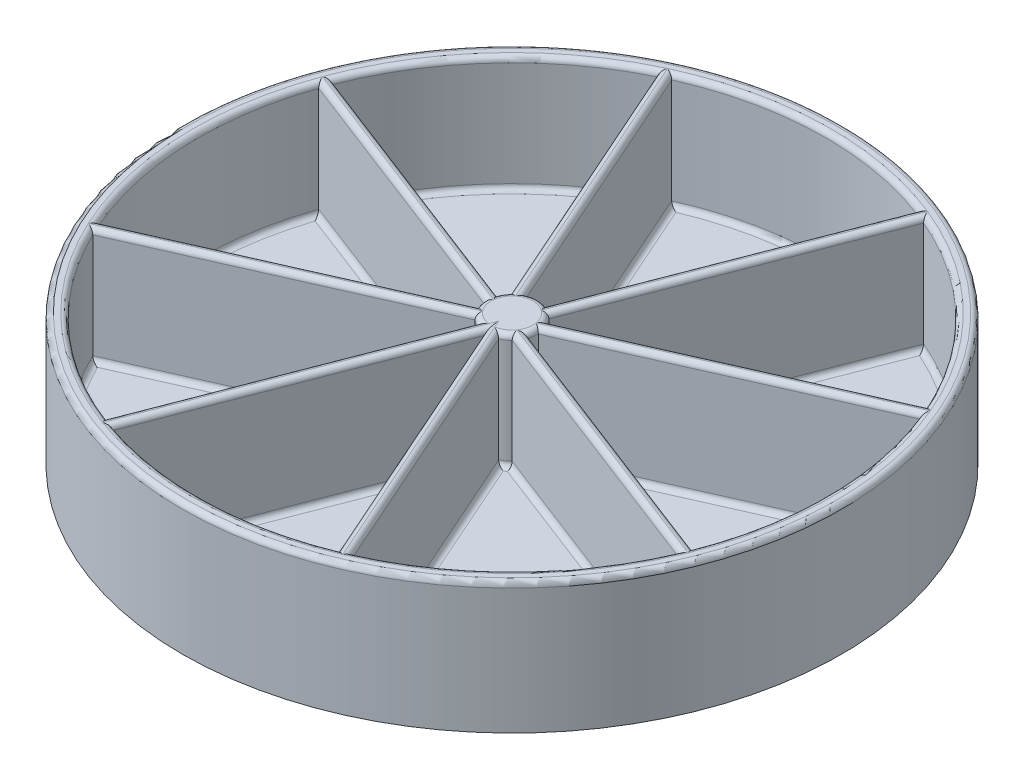
SolidWorks part; units mm, degrees
ref_plane "Front Plane" through (0, 0, 0) normal (0, 0, 1) x (1, 0, 0)
ref_plane "Top Plane" through (0, 0, 0) normal (0, 1, 0) x (1, 0, 0)
ref_plane "Right Plane" through (0, 0, 0) normal (1, 0, 0) x (0, 0, -1)
sketch "Sketch1" plane through (0, 0, 0) normal (0, 1, 0) x (1, 0, 0)
  circle A0 centre (0, 0) radius 63
extrude "Boss-Extrude1" add sketch "Sketch1" along normal blind 25
sketch "Sketch2" plane through (0, 25, 0) normal (0, 1, 0) x (1, 0, 0)
  circle A0 centre (0, 0) radius 60
extrude "Cut-Extrude1" cut sketch "Sketch2" against normal blind 22
sketch "Sketch3" plane through (0, 3, 0) normal (0, 1, 0) x (1, 0, 0)
  line L0 (-24.3169, 54.8515) -> (24.3169, -54.8515)
  line L1 (21.5912, 55.9805) -> (-24.3169, 54.8515)
  line L2 (-24.3169, 54.8515) -> (-55.9805, 21.5912)
  line L3 (-55.9805, 21.5912) -> (-54.8515, -24.3169)
  line L4 (-54.8515, -24.3169) -> (-21.5912, -55.9805)
  line L5 (-21.5912, -55.9805) -> (24.3169, -54.8515)
  line L6 (24.3169, -54.8515) -> (55.9805, -21.5912)
  line L7 (55.9805, -21.5912) -> (54.8515, 24.3169)
  line L8 (54.8515, 24.3169) -> (21.5912, 55.9805)
  line L9 (-21.5912, -55.9805) -> (21.5912, 55.9805)
  line L10 (-54.8515, -24.3169) -> (54.8515, 24.3169)
  line L11 (-55.9805, 21.5912) -> (55.9805, -21.5912)
  circle A0 centre (0, 0) radius 55.4328 construction
extrude "Extrude-Thin2" add sketch "Sketch3" along normal blind 22 thin contours L0 | L11 | L10 | L9 thin type one direction wall 2
sketch "Sketch4" plane through (0, 0, 0) normal (0, -1, 0) x (1, 0, 0)
  circle A0 centre (0, 0) radius 5
extrude "Boss-Extrude2" add sketch "Sketch4" against normal blind 25
fillet "Fillet1" radius 1 63 edges at (-11.6953, 3, 30.3228) (11.6953, 3, -30.3228) (-40.6404, 3, 44.1402) (-28.6946, 3, 14.9087) (30.3158, 3, -11.2519) (-2.6349, 3, 4.2494) (-9.7924, 3, 30.9469) (11.3017, 3, 30.4281) (1.4751, 3, 59.9819) (-30.8322, 3, -9.7481) (29.3928, 3, 13.4802) (42.761, 3, 42.0892) (-13.1716, 3, -29.7112) (13.1716, 3, 29.7112) (2.8406, 3, 4.1147) (59.9981, 3, -0.4751) (-30.3228, 3, -11.6953) (30.3228, 3, 11.6953) (4.9182, 3, 0.9009) (13.4802, 3, -29.3928) (42.0892, 3, -42.761) (-29.7112, 3, 13.1716) (29.7112, 3, -13.1716) (4.1147, 3, -2.8406) (-1.4751, 3, -59.9819) (-0.1229, 3, -4.9985) (-44.1402, 3, -40.6404) (-14.9087, 3, -28.6946) (-4.2494, 3, -2.6349) (-59.9489, 3, 2.4747) (-4.8679, 3, 1.1416) (0, 25, 63) (-9.7924, 25, 30.9469) (1.4751, 25, 59.9819) (11.3017, 25, 30.4281) (-13.1716, 25, -29.7112) (13.1716, 25, 29.7112) (42.761, 25, 42.0892) (-30.8322, 25, -9.7481) (29.3928, 25, 13.4802) (2.8406, 25, 4.1147) (-40.6404, 25, 44.1402) (-11.6953, 25, 30.3228) (11.6953, 25, -30.3228) (-2.6349, 25, 4.2494) (-28.6946, 25, 14.9087) (30.3158, 25, -11.2519) (-59.9489, 25, 2.4747) (-29.7112, 25, 13.1716) (29.7112, 25, -13.1716) (-4.8679, 25, 1.1416) (-44.1402, 25, -40.6404) (-30.3228, 25, -11.6953) (30.3228, 25, 11.6953) (-4.2494, 25, -2.6349) (-14.9087, 25, -28.6946) (-1.4751, 25, -59.9819) (-0.1229, 25, -4.9985) (42.0892, 25, -42.761) (13.4802, 25, -29.3928) (4.1147, 25, -2.8406) (59.9981, 25, -0.4751) (4.9182, 25, 0.9009)
sketch "Sketch5" plane through (0, 0, 0) normal (0, -1, 0) x (1, 0, 0)
  line L1 (-3.15, -1.4) -> (3.15, -1.4)
  line L2 (-3.15, -1.4) -> (-3.15, 1.4)
  line L3 (-3.15, 1.4) -> (3.15, 1.4)
  line L4 (3.15, -1.4) -> (3.15, 1.4)
  line L5 (-3.15, -1.4) -> (3.15, 1.4) construction
  line L6 (-3.15, 1.4) -> (3.15, -1.4) construction
  point P0 (0, 0)
  dimension "D1" = 2.8
  dimension "D2" = 6.3
extrude "Cut-Extrude2" cut sketch "Sketch5" against normal blind 6
